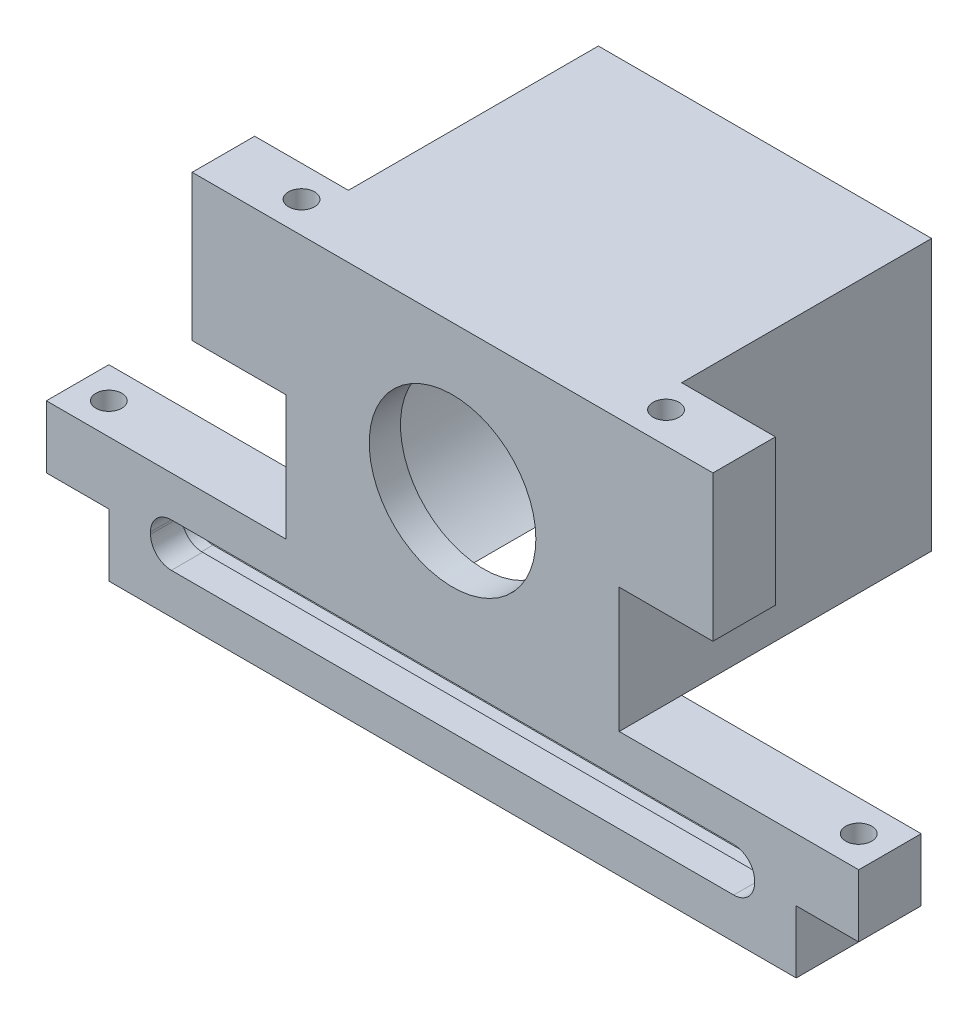
SolidWorks part; units mm, degrees
material "1060 Alloy"
ref_plane "Front Plane" through (0, 0, 0) normal (0, 0, 1) x (1, 0, 0)
ref_plane "Top Plane" through (0, 0, 0) normal (0, 1, 0) x (1, 0, 0)
ref_plane "Right Plane" through (0, 0, 0) normal (1, 0, 0) x (0, 0, -1)
sketch "Sketch1" plane through (0, 0, 0) normal (0, 0, 1) x (1, 0, 0)
  line L0 (23, 32) -> (55, 32)
  line L1 (6, 0) -> (6, -6)
  line L2 (55, 32) -> (55, 6)
  line L3 (23, 32) -> (23, 6)
  line L4 (10, 2.1) -> (68, 2.1)
  line L5 (10, 2.1) -> (10, -2.1)
  line L6 (10, -2.1) -> (68, -2.1)
  line L7 (68, 2.1) -> (68, -2.1)
  line L8 (6, -6) -> (72, -6)
  line L9 (72, -6) -> (72, 0)
  line L10 (6, 0) -> (0, 0)
  line L11 (0, 0) -> (0, 6)
  line L12 (0, 6) -> (23, 6)
  line L13 (55, 6) -> (78, 6)
  line L14 (78, 6) -> (78, 0)
  line L15 (78, 0) -> (72, 0)
  circle A0 centre (39, 18) radius 8
  dimension "D4" = 16
  dimension "D1" = 4.2
  dimension "D2" = 58
  dimension "D3" = 3.9
  dimension "D5" = 4
  dimension "D6" = 4
  dimension "D7" = 32
  dimension "D8" = 16
  dimension "D9" = 18
  dimension "D10" = 6
  dimension "D12" = 6
  dimension "D13" = 3.9
  dimension "D14" = 32
extrude "Boss-Extrude1" add sketch "Sketch1" along normal blind 30
sketch "Sketch3" plane through (0, 0, 0) normal (0, 0, -1) x (-1, 0, 0)
  circle A0 centre (-39, 18) radius 13
  dimension "D1" = 26
extrude "Cut-Extrude2" cut sketch "Sketch3" against normal offset from surface (27 mm away) 3 up to face at (39, 0, 30)
hole_wizard "Tap Drill for M3 Tap2" positions "Sketch5" profile "Sketch4" hole size "M3" standard "ISO"
sketch "Sketch5" plane through (38.1016, 0, -22.7468) normal (0, -1, 0) x (-1, 0, 0)
  line L3 (-39.8984, -52.7468) -> (-39.8984, -22.7468) construction
  line L4 (38.1016, -52.7468) -> (38.1016, -22.7468) construction
  line L5 (-33.8984, -52.7468) -> (-39.8984, -52.7468) construction
  point P0 (35.1016, -49.7468)
  point P2 (-36.8984, -49.7468)
  dimension "D1" = 3
  dimension "D2" = 3
  dimension "D3" = 3
sketch "Sketch4" plane through (3, 0, 27) normal (1, 0, 0) x (0, 0, -1)
  line L0 (0, 0) -> (0, 8.7511)
  line L1 (0, 8.7511) -> (1.25, 8)
  line L2 (1.25, 8) -> (1.25, 0)
  line L5 (1.25, 0) -> (0, 0)
  line L10 (0, 8.7511) -> (-1.25, 8) construction
  line L11 (0, -6.35) -> (0, 107.95) construction
  dimension "Hole Dia." = 2.5
  dimension "Hole Depth" = 8
  dimension "Drill Angle" = 118
sketch "Sketch6" plane through (0, 0, 0) normal (0, 0, -1) x (-1, 0, 0)
  line L2 (-78, 6) -> (0, 6)
  line L3 (-78, 6) -> (-78, -6)
  line L4 (-78, -6) -> (0, -6)
  line L5 (0, 6) -> (0, -6)
extrude "Cut-Extrude3" cut sketch "Sketch6" along direction (0, 0, 1) on the side against the normal offset from surface (24 mm away) 6 up to face at (39, 0, 30)
sketch "Sketch10" plane through (0, 0, 24) normal (0, 0, -1) x (-1, 0, 0)
  line L1 (-70, 4) -> (-8, 4)
  line L2 (-70, 4) -> (-70, -4)
  line L3 (-70, -4) -> (-8, -4)
  line L4 (-8, 4) -> (-8, -4)
  line L5 (-68, 2.1) -> (-10, 2.1) construction
  line L6 (-68, -2.1) -> (-68, 2.1) construction
  line L7 (-10, 2.1) -> (-10, -2.1) construction
  dimension "D1" = 8
  dimension "D2" = 1.9
  dimension "D3" = 2
  dimension "D4" = 2
extrude "Cut-Extrude5" cut sketch "Sketch10" against normal blind 3
sketch "Sketch11" plane through (0, 0, 30) normal (0, 0, 1) x (1, 0, 0)
  line L0 (23, 6) -> (0, 6) construction
  line L1 (23, 32) -> (14, 32)
  line L2 (23, 32) -> (23, 6)
  line L3 (23, 6) -> (14, 6)
  line L4 (14, 32) -> (14, 6)
  line L5 (78, 6) -> (55, 6) construction
  line L6 (55, 32) -> (64, 32)
  line L7 (55, 32) -> (55, 6)
  line L8 (55, 6) -> (64, 6)
  line L9 (64, 32) -> (64, 6)
  dimension "D1" = 50
extrude "Boss-Extrude2" add sketch "Sketch11" against normal up to surface (6 mm away) up to face at (39, 0, 24)
sketch "Sketch12" plane through (0, 0, 24) normal (0, 0, -1) x (-1, 0, 0)
  line L0 (-55, 6) -> (-55, 32) construction
  line L1 (-64, 6) -> (-55, 6)
  line L2 (-64, 6) -> (-64, 18)
  line L3 (-64, 18) -> (-55, 18)
  line L4 (-55, 6) -> (-55, 18)
  line L5 (-23, 32) -> (-23, 6) construction
  line L6 (-14, 6) -> (-23, 6)
  line L7 (-14, 6) -> (-14, 18)
  line L8 (-14, 18) -> (-23, 18)
  line L9 (-23, 6) -> (-23, 18)
  dimension "D1" = 12
extrude "Cut-Extrude6" cut sketch "Sketch12" against normal up to next
fillet "Fillet1" radius 2 8 edges at (8, -4, 25.5) (10, -2.1, 28.5) (8, 4, 25.5) (10, 2.1, 28.5) (70, -4, 25.5) (70, 4, 25.5) (68, -2.1, 28.5) (68, 2.1, 28.5)
hole_wizard "M3x0.5 Tapped Hole1" positions "3DSketch1" profile "Sketch13" tap size "M3x0.5" standard "ANSI Metric"
sketch3d "3DSketch1"
  line L0 (55, 32, 24) -> (55, 32, 0) construction
  line L1 (55, 32, 24) -> (64, 32, 24) construction
  line L2 (14, 32, 24) -> (23, 32, 24) construction
  line L3 (23, 32, 24) -> (23, 32, 0) construction
  point P0 (56.5, 32, 27)
  point P2 (21.5, 32, 27)
  dimension "D1" = 1.5
  dimension "D2" = 3
  dimension "D3" = 3
  dimension "D4" = 1.5
sketch "Sketch13" plane through (56.5, 32, 27) normal (1, 0, 0) x (0, 0, 1)
  line L0 (0, 0) -> (0, 10.2511)
  line L1 (0, 10.2511) -> (1.25, 9.5)
  line L2 (1.25, 9.5) -> (1.25, 0)
  line L5 (1.25, 0) -> (0, 0)
  line L10 (0, 10.2511) -> (-1.25, 9.5) construction
  line L11 (0, -6.35) -> (0, 107.95) construction
  dimension "Tap Drill Dia." = 2.5
  dimension "Tap Drill Depth" = 9.5
  dimension "Drill Angle" = 118
cosmetic thread "Hole Thread1" parameters "D1"=8, "D2"=3
cosmetic thread "Hole Thread2" parameters "D1"=8, "D2"=3
